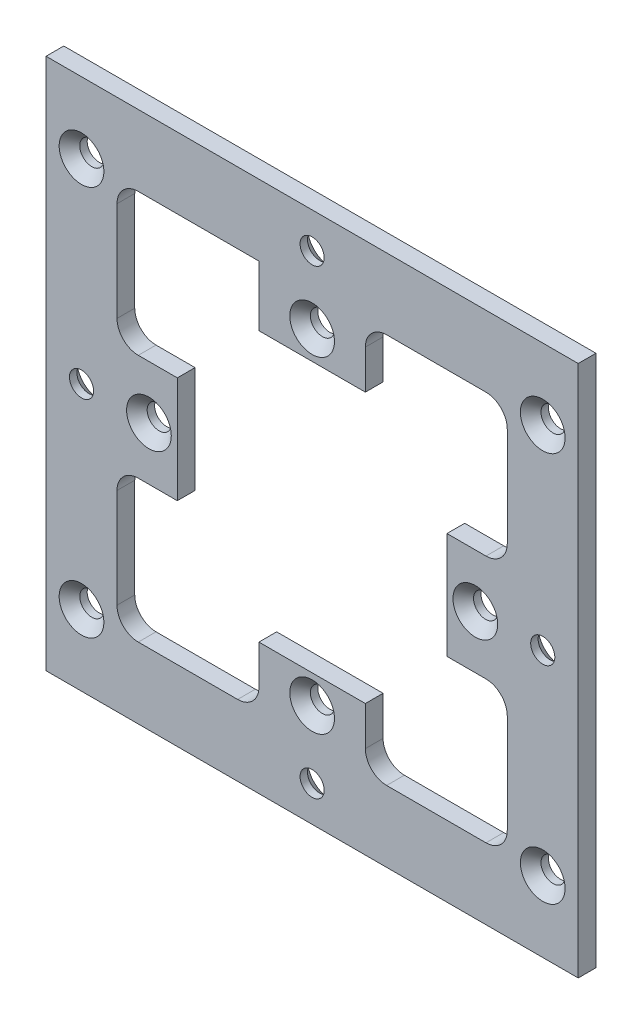
SolidWorks part; units mm, degrees
material "1060 Alloy"
ref_plane "Front Plane" through (0, 0, 0) normal (0, 0, 1) x (1, 0, 0)
ref_plane "Top Plane" through (0, 0, 0) normal (0, 1, 0) x (1, 0, 0)
ref_plane "Right Plane" through (0, 0, 0) normal (1, 0, 0) x (0, 0, -1)
sketch "Sketch1" plane through (0, 0, 0) normal (0, 0, 1) x (1, 0, 0)
  line L0 (37.5, 37.5) -> (-37.5, 37.5) construction
  line L1 (37.5, 0) -> (-37.5, 0)
  line L2 (37.5, 0) -> (37.5, 75)
  line L3 (37.5, 75) -> (-37.5, 75)
  line L4 (-37.5, 0) -> (-37.5, 75)
  line L5 (0, 0) -> (0, 75) construction
  line L7 (-24.5, 10) -> (24.5, 10)
  line L8 (-27.5, 13) -> (-27.5, 62)
  line L9 (-24.5, 65) -> (24.5, 65)
  line L10 (27.5, 13) -> (27.5, 62)
  line L11 (-27.5, 10) -> (27.5, 65) construction
  line L12 (-27.5, 65) -> (27.5, 10) construction
  arc A0 (-27.5, 62) -> (-24.5, 65) centre (-24.5, 62) cw
  arc A1 (24.5, 65) -> (27.5, 62) centre (24.5, 62) cw
  arc A2 (24.5, 10) -> (27.5, 13) centre (24.5, 13) ccw
  arc A3 (-24.5, 10) -> (-27.5, 13) centre (-24.5, 13) cw
  point P11 (0, 37.5)
  dimension "D2" = 3
  dimension "D3" = 3
  dimension "D1" = 10
extrude "Boss-Extrude1" add sketch "Sketch1" along normal blind 2.5
hole_wizard "CSK for M3 Oval Head Machine Screw1" positions "3DSketch1" profile "Sketch2" countersink size "M3" standard "Ansi Metric" end condition through all
sketch3d "3DSketch1"
  line L0 (-37.5, 0, 2.5) -> (37.5, 0, 2.5) construction
  line L1 (37.5, 75, 2.5) -> (-37.5, 75, 2.5) construction
  line L2 (37.5, 0, 2.5) -> (37.5, 75, 2.5) construction
  line L3 (-37.5, 75, 2.5) -> (-37.5, 0, 2.5) construction
  point P0 (32.5, 10, 2.5)
  point P2 (-32.5, 10, 2.5)
  point P4 (-32.5, 65, 2.5)
  point P6 (32.5, 65, 2.5)
  dimension "D1" = 10
  dimension "D2" = 10
  dimension "D3" = 5
  dimension "D4" = 5
sketch "Sketch2" plane through (32.5, 10, 2.5) normal (1, 0, 0) x (0, -1, 0)
  line L0 (0, 0) -> (0, 2.5)
  line L1 (0, 2.5) -> (1.7, 2.5)
  line L2 (1.7, 2.5) -> (1.7, 1.45)
  line L3 (1.7, 1.45) -> (3.15, 0)
  line L5 (3.15, 0) -> (0, 0)
  line L6 (-1.7, 1.45) -> (-3.15, 0) construction
  line L11 (0, -6.35) -> (0, 107.95) construction
  dimension "Thru Hole Dia." = 3.4
  dimension "Thru Hole Depth" = 2.5
  dimension "Near C'Sink Dia." = 6.3
  dimension "Near C'Sink Angle" = 90
hole_wizard "CSK for M3 Oval Head Machine Screw2" positions "Sketch4" profile "Sketch3" countersink size "M3" standard "Ansi Metric" end condition through all
sketch "Sketch4" plane through (0, 0, 0) normal (0, 0, -1) x (-1, 0, 0)
  line L8 (0, 0) -> (0, 10) construction
  line L9 (24.5, 10) -> (-24.5, 10) construction
  line L11 (-27.5, 37.5) -> (-37.5, 37.5) construction
  line L12 (-27.5, 13) -> (-27.5, 62) construction
  line L13 (-37.5, 0) -> (-37.5, 75) construction
  line L15 (37.5, 37.5) -> (27.5, 37.5) construction
  line L16 (37.5, 75) -> (37.5, 0) construction
  line L17 (27.5, 62) -> (27.5, 13) construction
  line L19 (0, 65) -> (0, 75) construction
  line L20 (-24.5, 65) -> (24.5, 65) construction
  line L21 (-37.5, 75) -> (37.5, 75) construction
  point P53 (0, 5)
  point P55 (32.5, 37.5)
  point P57 (-32.5, 37.5)
  point P59 (0, 70)
sketch "Sketch3" plane through (0, 5, 0) normal (1, 0, 0) x (0, 1, 0)
  line L0 (0, 0) -> (0, 2.5)
  line L1 (0, 2.5) -> (1.7, 2.5)
  line L2 (1.7, 2.5) -> (1.7, 1.45)
  line L3 (1.7, 1.45) -> (3.15, 0)
  line L5 (3.15, 0) -> (0, 0)
  line L6 (-1.7, 1.45) -> (-3.15, 0) construction
  line L11 (0, -6.35) -> (0, 107.95) construction
  dimension "Thru Hole Dia." = 3.4
  dimension "Thru Hole Depth" = 2.5
  dimension "Near C'Sink Dia." = 6.3
  dimension "Near C'Sink Angle" = 90
sketch "Sketch5" plane through (0, 0, 2.5) normal (0, 0, 1) x (1, 0, 0)
  line L0 (0, 0) -> (0, 75) construction
  line L1 (37.5, 75) -> (-37.5, 75) construction
  line L2 (37.5, 37.5) -> (-37.5, 37.5) construction
  line L3 (37.5, 0) -> (37.5, 75) construction
  line L4 (-37.5, 75) -> (-37.5, 0) construction
  line L5 (-24.5, 10) -> (24.5, 10) construction
  line L6 (-7.5, 10) -> (7.5, 10)
  line L7 (-7.5, 10) -> (-7.5, 18.5)
  line L8 (-7.5, 18.5) -> (7.5, 18.5)
  line L9 (7.5, 10) -> (7.5, 18.5)
  line L10 (-7.5, 10) -> (7.5, 18.5) construction
  line L11 (-7.5, 18.5) -> (7.5, 10) construction
  line L12 (-7.5, 56.5) -> (7.5, 65) construction
  line L13 (-7.5, 65) -> (7.5, 56.5) construction
  line L14 (7.5, 65) -> (7.5, 56.5)
  line L15 (-7.5, 56.5) -> (7.5, 56.5)
  line L16 (-7.5, 65) -> (-7.5, 56.5)
  line L17 (-7.5, 65) -> (7.5, 65)
  line L18 (37.5, 0) -> (-37.5, 75) construction
  line L19 (19, 45) -> (27.5, 30) construction
  line L20 (27.5, 45) -> (19, 30) construction
  line L21 (27.5, 30) -> (19, 30)
  line L22 (19, 45) -> (19, 30)
  line L23 (27.5, 45) -> (19, 45)
  line L24 (27.5, 45) -> (27.5, 30)
  line L25 (-27.5, 45) -> (-19, 30) construction
  line L26 (-19, 45) -> (-27.5, 30) construction
  line L27 (-27.5, 45) -> (-27.5, 30)
  line L28 (-27.5, 45) -> (-19, 45)
  line L29 (-19, 45) -> (-19, 30)
  line L30 (-27.5, 30) -> (-19, 30)
  circle A0 centre (0, 37.5) radius 19 construction
  point P11 (0, 14.25)
  point P24 (0, 60.75)
  point P33 (23.25, 37.5)
  point P38 (-23.25, 37.5)
  dimension "D1" = 15
extrude "Boss-Extrude2" add sketch "Sketch5" against normal up to surface (2.5 mm away) up to face at (-35.65, 37.5, 0)
fillet "Fillet1" radius 3 7 edges at (-7.5, 10, 1.25) (-27.5, 30, 1.25) (-27.5, 45, 1.25) (7.5, 65, 1.25) (27.5, 45, 1.25) (27.5, 30, 1.25) (7.5, 10, 1.25)
hole_wizard "CSK for M3 Oval Head Machine Screw3" positions "Sketch7" profile "Sketch6" countersink size "M3" standard "Ansi Metric" end condition through all
sketch "Sketch7" plane through (0, 0, 2.5) normal (0, 0, 1) x (1, 0, 0)
  line L5 (19, 37.5) -> (37.5, 37.5) construction
  line L6 (19, 45) -> (19, 30) construction
  line L7 (37.5, 0) -> (37.5, 75) construction
  line L9 (0, 56.5) -> (0, 75) construction
  line L10 (-7.5, 56.5) -> (7.5, 56.5) construction
  line L11 (37.5, 75) -> (-37.5, 75) construction
  line L13 (-19, 37.5) -> (-37.5, 37.5) construction
  line L14 (-19, 30) -> (-19, 45) construction
  line L15 (-37.5, 75) -> (-37.5, 0) construction
  line L17 (0, 18.5) -> (0, 0) construction
  line L18 (7.5, 18.5) -> (-7.5, 18.5) construction
  line L19 (-37.5, 0) -> (37.5, 0) construction
  point P0 (0, 14.5)
  point P45 (23, 37.5)
  point P47 (0, 60.5)
  point P49 (-23, 37.5)
  dimension "D1" = 4
  dimension "D2" = 4
  dimension "D3" = 4
  dimension "D4" = 4
sketch "Sketch6" plane through (0, 14.5, 2.5) normal (1, 0, 0) x (0, -1, 0)
  line L0 (0, 0) -> (0, 2.5)
  line L1 (0, 2.5) -> (1.7, 2.5)
  line L2 (1.7, 2.5) -> (1.7, 1.45)
  line L3 (1.7, 1.45) -> (3.15, 0)
  line L5 (3.15, 0) -> (0, 0)
  line L6 (-1.7, 1.45) -> (-3.15, 0) construction
  line L11 (0, -6.35) -> (0, 107.95) construction
  dimension "Thru Hole Dia." = 3.4
  dimension "Thru Hole Depth" = 2.5
  dimension "Near C'Sink Dia." = 6.3
  dimension "Near C'Sink Angle" = 90
